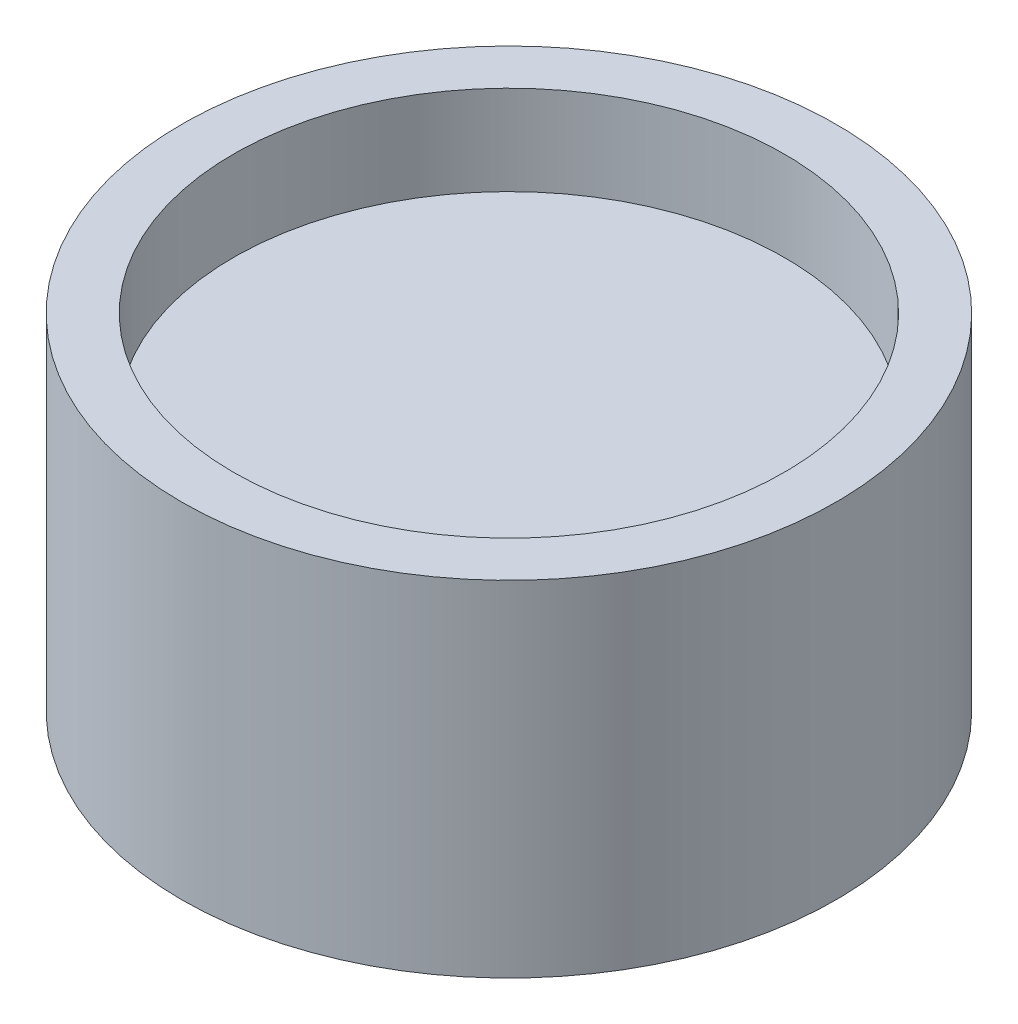
SolidWorks part; units mm, degrees
material "6061-T6 (SS)"
ref_plane "Front Plane" through (0, 0, 0) normal (0, 0, 1) x (1, 0, 0)
ref_plane "Top Plane" through (0, 0, 0) normal (0, 1, 0) x (1, 0, 0)
ref_plane "Right Plane" through (0, 0, 0) normal (1, 0, 0) x (0, 0, -1)
sketch "Sketch1" plane through (0, 0, 0) normal (0, 0, 1) x (1, 0, 0)
  line L11 (0, 0) -> (-60.325, 0)
  line L12 (-60.325, 0) -> (-60.325, 31.75)
  line L13 (-60.325, 31.75) -> (-50.8, 31.75)
  line L14 (0, 0) -> (0, 15.24)
  line L15 (0, 15.24) -> (-50.8, 15.24)
  line L16 (-50.8, 15.24) -> (-50.8, 31.75)
  line L17 (0, 0) -> (0, -15.24)
  line L18 (-60.325, 0) -> (-60.325, -31.75)
  line L19 (-60.325, -31.75) -> (-50.8, -31.75)
  line L20 (-50.8, -31.75) -> (-50.8, -15.24)
  line L21 (-50.8, -15.24) -> (0, -15.24)
  line L22 (0, 31.75) -> (0, -31.75) construction
  dimension "D1" = 60.325
revolve "Revolve1" add sketch "Sketch1" angle 360 about L22 region at (-33.8726, -9.9388, 0) region at (-33.8726, 9.9388, 0)
